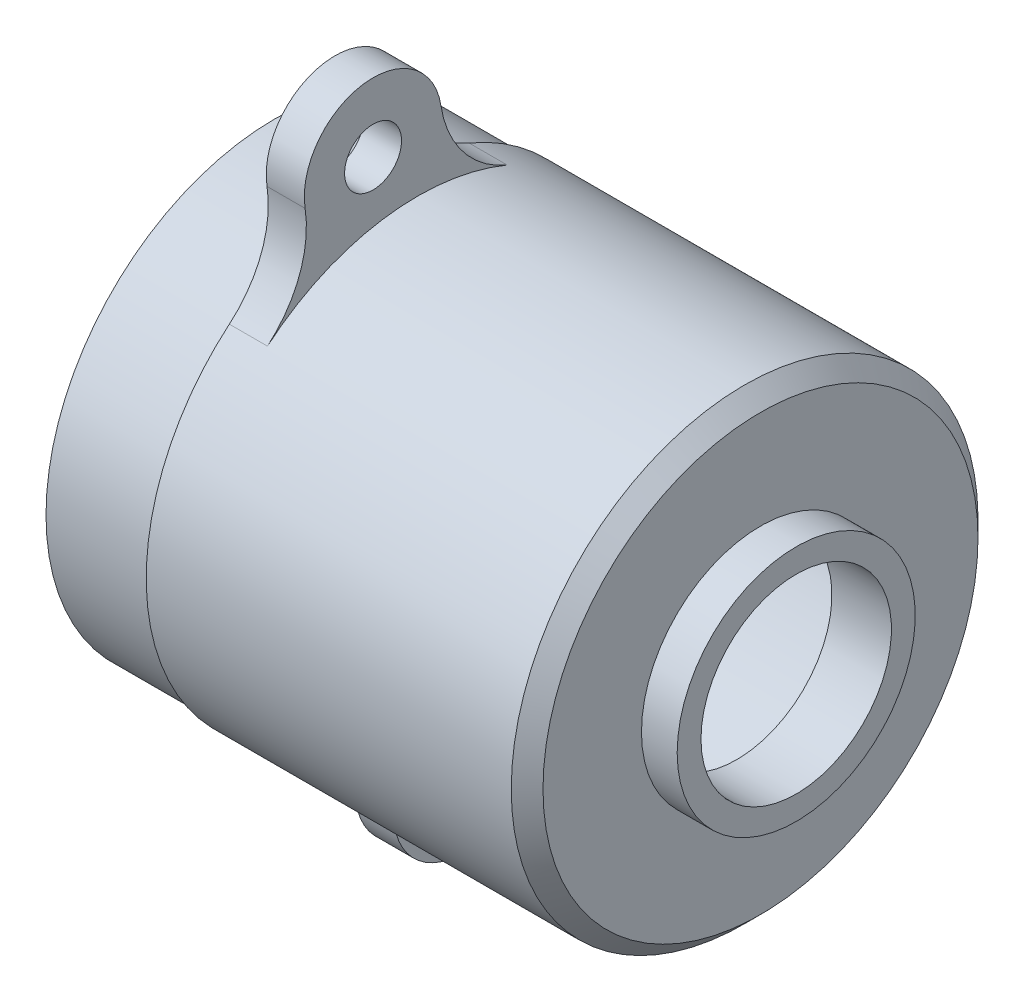
SolidWorks part; units mm, degrees
material "6061-T6 (SS)"
ref_plane "Front Plane" through (0, 0, 0) normal (0, 0, 1) x (1, 0, 0)
ref_plane "Top Plane" through (0, 0, 0) normal (0, 1, 0) x (1, 0, 0)
ref_plane "Right Plane" through (0, 0, 0) normal (1, 0, 0) x (0, 0, -1)
other "Center of Mass"
ref_plane "Plane3" through (-27.4281, 0, 0) normal (1, 0, 0) x (0, 0, -1)
ref_plane "Plane4" through (-3.6156, 0, 0) normal (1, 0, 0) x (0, 0, -1)
sketch "Sketch1" plane through (-27.4281, 0, 0) normal (1, 0, 0) x (0, 0, -1)
  line L0 (0, 0) -> (-2.9763, 19.3027) construction
  line L1 (-0.1069, 15.7295) -> (1.5529, 20.0011) construction
  line L2 (1.5529, 20.0011) -> (-1.3165, 23.5743) construction
  line L3 (-1.3165, 23.5743) -> (-5.8456, 22.876) construction
  line L4 (-5.8456, 22.876) -> (-7.5055, 18.6044) construction
  line L5 (-7.5055, 18.6044) -> (-4.6361, 15.0312) construction
  line L6 (-4.6361, 15.0312) -> (-0.1069, 15.7295) construction
  line L7 (4.6361, -15.0312) -> (0.1069, -15.7295) construction
  line L8 (0.1069, -15.7295) -> (-1.5529, -20.0011) construction
  line L9 (-1.5529, -20.0011) -> (1.3165, -23.5743) construction
  line L10 (1.3165, -23.5743) -> (5.8456, -22.876) construction
  line L11 (5.8456, -22.876) -> (7.5055, -18.6044) construction
  line L12 (7.5055, -18.6044) -> (4.6361, -15.0312) construction
  line L13 (-7.5055, 18.6044) -> (1.5529, 20.0011) construction
  line L15 (0, 0) -> (11.8051, 1.8202) construction
  circle A0 centre (0, 0) radius 13.9746
  circle A1 centre (0, 0) radius 15.5621 construction
  circle A3 centre (2.9763, -19.3027) radius 3.9688 construction
  arc A8 (-10.0197, 11.9073) -> (-5.9677, -14.3724) centre (0, 0) ccw
  arc A9 (5.9677, 14.3724) -> (10.0197, -11.9073) centre (0, 0) cw
  circle A16 centre (-2.9763, 19.3027) radius 2.667 construction
  circle A17 centre (2.9763, -19.3027) radius 2.667 construction
  circle A19 centre (-2.9763, 19.3027) radius 2.1526 construction
  arc A20 (-10.0197, 11.9073) -> (-7.5055, 18.6044) centre (-14.7192, 17.4921) ccw
  arc A21 (-7.5055, 18.6044) -> (1.5529, 20.0011) centre (-2.9763, 19.3027) cw
  arc A22 (1.5529, 20.0011) -> (5.9677, 14.3724) centre (8.7667, 21.1134) ccw
  arc A23 (7.5055, -18.6044) -> (10.0197, -11.9073) centre (14.7192, -17.4921) cw
  arc A24 (-1.5529, -20.0011) -> (7.5055, -18.6044) centre (2.9763, -19.3027) ccw
  arc A25 (-5.9677, -14.3724) -> (-1.5529, -20.0011) centre (-8.7667, -21.1134) cw
  circle A27 centre (-2.9763, 19.3027) radius 2.1526 construction
  point P4 (-2.3715, 15.3803)
  dimension "D1" = 27.9492
  dimension "D4" = 5.334
  dimension "D2" = 1.5875
  dimension "D3" = 7.9375
extrude "Boss-Extrude1" add sketch "Sketch1" along normal blind 2.54
sketch "Sketch2" plane through (-24.8881, 0, 0) normal (1, 0, 0) x (0, 0, -1)
  circle A0 centre (0, 0) radius 13.9746
  circle A1 centre (0, 0) radius 15.5621
  arc A2 (-10.0197, 11.9073) -> (-5.9677, -14.3724) centre (0, 0) ccw construction
  circle A3 centre (0, 0) radius 13.9746 construction
extrude "Boss-Extrude2" add sketch "Sketch2" along normal up to surface (21.2725 mm away) up to plane "Plane4"
sketch "Sketch5" plane through (0, 0, 0) normal (0, 0, 1) x (1, 0, 0)
  line L1 (0.3531, 7.9375) -> (0.3531, 6.35)
  line L3 (-3.6156, -15.5621) -> (-3.6156, 15.5621) construction
  line L4 (-3.6156, 6.35) -> (-3.6156, 15.5621)
  line L5 (0, 0) -> (45.5597, 0) construction
  line L6 (-3.6156, 6.35) -> (0.3531, 6.35)
  line L9 (0.3531, 7.9375) -> (-2.0281, 7.9375)
  line L10 (-2.0281, 7.9375) -> (-2.0281, 14.5038)
  line L12 (-2.0281, 14.5038) -> (-3.0865, 15.5621)
  line L13 (-3.0865, 15.5621) -> (-3.6156, 15.5621)
  line L14 (-3.6156, 13.9746) -> (-2.5573, 15.0329) construction
  dimension "D2" = 3.9688
  dimension "D1" = 12.7
  dimension "D3" = 1.5875
  dimension "D4" = 1.5875
revolve "Revolve1" add sketch "Sketch5" angle 360 about L5
sketch "Sketch3" plane through (-27.4281, 0, 0) normal (-1, 0, 0) x (0, 0, 1)
  circle A0 centre (0, 0) radius 13.9746
  circle A1 centre (0, 0) radius 15.2446
  circle A2 centre (0, 0) radius 13.9746 construction
  dimension "D1" = 1.27
extrude "Boss-Extrude3" add sketch "Sketch3" along normal blind 7
sketch "Sketch6" [suppressed] plane through (0, 0, 0) normal (0, 0, 1) x (1, 0, 0)
  line L0 (-25.4, -23.8855) -> (-25.2167, -23.8855)
  line L1 (-18.1358, -23.8855) -> (-15.5958, -23.8855) construction
  line L2 (-25.4, -23.8855) -> (-25.4, -25.4)
  line L3 (-18.1358, -18.6044) -> (-18.1358, -23.8855) construction
  arc A0 (-25.4, -25.4) -> (-25.087, -27.369) centre (-19.05, -25.4) ccw construction
  arc A1 (-25.2167, -23.8855) -> (-25.4, -25.4) centre (-19.05, -25.4) cw
extrude "Copying Eruption" [suppressed] cut sketch "Sketch6" against normal through all both and the other way through all
hole_wizard "#6 Clearance Hole1" positions "Sketch7" profile "Sketch8" hole size "#6" standard "ANSI Inch" end condition up to next
sketch "Sketch7" plane through (-24.8881, 0, 0) normal (1, 0, 0) x (0, 0, -1)
  point P0 (-2.9763, 19.3027)
  point P3 (2.9763, -19.3027)
sketch "Sketch8" plane through (-24.8881, 19.3027, 2.9763) normal (0, 1, 0) x (0, 0, -1)
  line L0 (0, 0) -> (0, 2.54)
  line L1 (0, 2.54) -> (1.8986, 2.54)
  line L2 (1.8986, 2.54) -> (1.8986, 0)
  line L5 (1.8986, 0) -> (0, 0)
  line L11 (0, -6.35) -> (0, 107.95) construction
  dimension "Thru Hole Dia." = 3.7973
  dimension "Thru Hole Depth" = 2.54
equation "\"motor diameter\"= 28mm"
equation "\"D1@Sketch1\"=\"motor diameter\"-0.002in"
equation "\"D1@Boss-Extrude3\"=7mm"
equation "\"D2@Sketch5\"=5/32"
